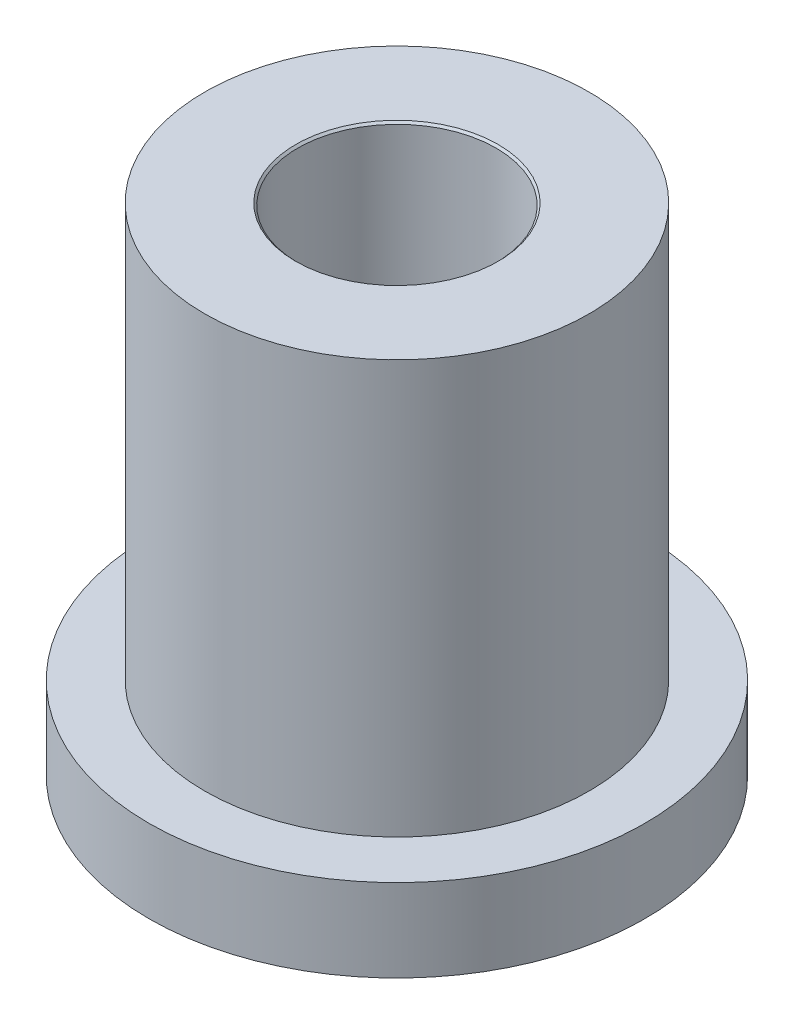
SolidWorks part; units mm, degrees
ref_plane "Front Plane" through (0, 0, 0) normal (0, 0, 1) x (1, 0, 0)
ref_plane "Top Plane" through (0, 0, 0) normal (0, 1, 0) x (1, 0, 0)
ref_plane "Right Plane" through (0, 0, 0) normal (1, 0, 0) x (0, 0, -1)
sketch "Sketch1" plane through (0, 0, 0) normal (0, 1, 0) x (1, 0, 0)
  circle A0 centre (0, 0) radius 3
  dimension "D1" = 6
extrude "Boss-Extrude1" add sketch "Sketch1" along normal blind 1
sketch "Sketch2" plane through (0, 1, 0) normal (0, 1, 0) x (1, 0, 0)
  circle A0 centre (0, 0) radius 2.325
  dimension "D1" = 4.65
extrude "Boss-Extrude2" add sketch "Sketch2" along normal blind 5
hole_wizard "M2 Clearance Hole1" positions "Sketch6" profile "Sketch5" hole size "M2" standard "ANSI Metric" end condition through all
sketch "Sketch6" plane through (0, 6, 0) normal (0, 1, 0) x (1, 0, 0)
  point P0 (0, 0)
sketch "Sketch5" plane through (0, 6, 0) normal (1, 0, 0) x (0, 0, 1)
  line L0 (0, 0) -> (0, 6)
  line L1 (0, 6) -> (1.2, 6)
  line L2 (1.2, 6) -> (1.2, 0.025)
  line L3 (1.2, 0.025) -> (1.225, 0)
  line L5 (1.225, 0) -> (0, 0)
  line L6 (-1.2, 0.025) -> (-1.225, 0) construction
  line L11 (0, -6.35) -> (0, 107.95) construction
  dimension "Thru Hole Dia." = 2.4
  dimension "Thru Hole Depth" = 6
  dimension "Near C'Sink Dia." = 2.45
  dimension "Near C'Sink Angle" = 90
